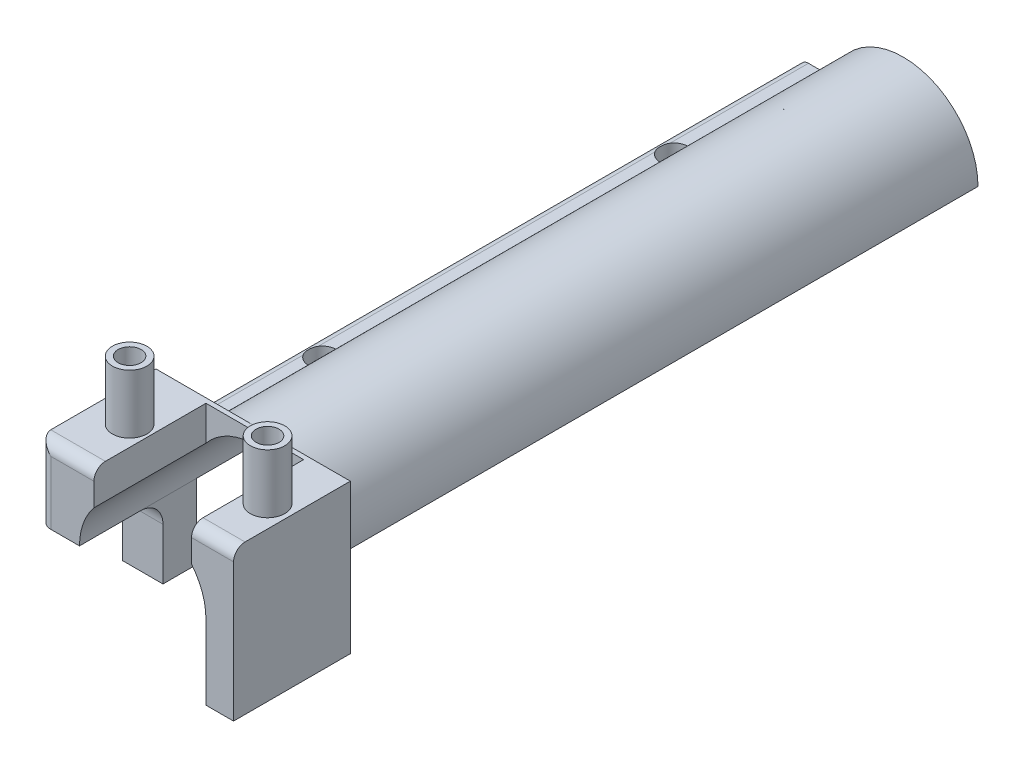
SolidWorks part; units mm, degrees
material "ABS"
ref_plane "X-Y Datum" through (0, 0, 0) normal (0, 0, 1) x (1, 0, 0)
ref_plane "X-Z Datum" through (0, 0, 0) normal (0, 1, 0) x (1, 0, 0)
ref_plane "Y-Z Datum" through (0, 0, 0) normal (1, 0, 0) x (0, 0, -1)
sketch "Sketch1" plane through (0, 0, 0) normal (0, 0, 1) x (1, 0, 0)
  line L0 (-13, 0) -> (-18, 0)
  line L1 (-18, 0) -> (-18, -13)
  line L2 (-18, -13) -> (0, -13)
  line L3 (-13, 0) -> (13, 0)
  line L4 (0, 13) -> (-18, 13)
  line L5 (-18, 13) -> (-18, 0)
  line L6 (-18, 3.81) -> (-12.4292, 3.81)
  circle A0 centre (0, 0) radius 13
  circle A1 centre (0, 0) radius 11
  dimension "D3" = 2
  dimension "D2" = 22
  dimension "D1" = 5
  dimension "D4" = 3.81
extrude "Boss-Extrude1" add sketch "Sketch1" along normal blind 112 contours A1 L3 A0 | A0 L6 L5 L0 region at (-12.569, 1.8832, 0) region at (-15.4029, 1.9398, 0)
sketch "Sketch5" plane through (0, 3.81, 0) normal (0, 1, 0) x (1, 0, 0)
  point P0 (-14.5, -86.6)
  point P1 (-14.5, -25.4)
hole_wizard "M4 Clearance Hole2" positions "Sketch5" profile "Sketch6" hole size "M4" standard "ANSI Metric" end condition through all
sketch "Sketch6" plane through (-14.5, 3.81, 86.6) normal (1, 0, 0) x (0, 0, 1)
  line L0 (0, 0) -> (0, 3.81)
  line L1 (0, 3.81) -> (2.4, 3.81)
  line L2 (2.4, 3.81) -> (2.4, 0)
  line L5 (2.4, 0) -> (0, 0)
  line L11 (0, -6.35) -> (0, 107.95) construction
  dimension "Thru Hole Dia." = 4.8
  dimension "Thru Hole Depth" = 3.81
sketch "Sketch7" plane through (0, 3.81, 0) normal (0, 1, 0) x (1, 0, 0)
  circle A0 centre (-14.5, -25.4) radius 4
  circle A1 centre (-14.5, -86.6) radius 4
  dimension "D1" = 8
extrude "Cut-Extrude1" cut sketch "Sketch7" along normal through all
fillet "Fillet1" radius 1.5 4 edges at (-12.4292, 3.81, 101.0111) (-12.4292, 3.81, 56) (-18, 3.81, 56) (-12.4292, 3.81, 10.9889)
sketch "Sketch10" plane through (0, 0, 112) normal (0, 0, 1) x (1, 0, 0)
  line L0 (-18, 0) -> (-11, 0) construction
  line L1 (-18, 0) -> (-11, 0)
  line L2 (-18, 2.31) -> (-18, 0) construction
  line L3 (11, 0) -> (13, 0) construction
  line L4 (11, 0) -> (13, 0)
  line L5 (-18, 2.31) -> (-18, 0)
  line L6 (-18, 2.31) -> (-18, 13)
  line L7 (-18, 13) -> (15.8008, 13)
  line L8 (15.8008, 13) -> (15.8008, 0)
  line L9 (15.8008, 0) -> (13, 0)
  arc A0 (11, 0) -> (-11, 0) centre (0, 0) ccw construction
  arc A1 (11, 0) -> (-11, 0) centre (0, 0) ccw
  arc A2 (-16.5, 3.81) -> (-18, 2.31) centre (-16.5, 2.31) ccw construction
  arc A3 (-13.4927, 3.81) -> (-12.0969, 4.7607) centre (-13.4927, 5.31) ccw construction
  arc A4 (13, 0) -> (-12.0969, 4.7607) centre (0, 0) ccw construction
  arc A5 (13, 0) -> (-12.0969, 4.7607) centre (0, 0) ccw
  arc A6 (-13.4927, 3.81) -> (-12.0969, 4.7607) centre (-13.4927, 5.31) ccw
  arc A7 (-16.5, 3.81) -> (-18, 2.31) centre (-16.5, 2.31) ccw
  point P13 (0, 13)
  line M2 (-13.4927, 3.81) -> (-16.5, 3.81)
  arc M3 (-16.5, 3.81) -> (-18, 2.31) centre (-16.5, 2.31) ccw
  line M4 (-18, 2.31) -> (-18, 0)
  line M5 (-18, 0) -> (-11, 0)
  arc M6 (-11, 0) -> (11, 0) centre (0, 0) cw
  line M7 (11, 0) -> (13, 0)
  arc M8 (13, 0) -> (-12.0969, 4.7607) centre (0, 0) ccw
  arc M9 (-12.0969, 4.7607) -> (-13.4927, 3.81) centre (-13.4927, 5.31) cw
extrude "Boss-Extrude2" add sketch "Sketch10" along normal blind 20.32 contours L7 M3 M2 M9 M8 | L7 M8 M9 M2 M3 M4 M5 M6 M7 | L8 M8 region at (-17.6638, 1.155, 112) region at (-13.147, 9.1854, 112) region at (12.2525, 8.2946, 112)
sketch "Sketch12" plane through (0, 13, 0) normal (0, 1, 0) x (1, 0, 0)
  circle A0 centre (12, -122.6) radius 2 construction
  circle A1 centre (-12, -122.6) radius 2 construction
  circle A2 centre (12, -122.6) radius 2
  circle A3 centre (-12, -122.6) radius 2
  circle A4 centre (-12, -122.6) radius 3
  circle A5 centre (12, -122.6) radius 3
  dimension "D1" = 6
  dimension "D2" = 6
extrude "Boss-Extrude4" add sketch "Sketch12" along normal blind 10.2375
sketch "Sketch13" plane through (0, 13, 0) normal (0, 1, 0) x (1, 0, 0)
  line L0 (0, -114.6) -> (0, -130.6) construction
  line L2 (-8.4946, -112.821) -> (8.4946, -112.821)
  line L3 (-8.4946, -112.821) -> (-8.4946, -132.379)
  line L4 (-8.4946, -132.379) -> (8.4946, -132.379)
  line L5 (8.4946, -112.821) -> (8.4946, -132.379)
  line L6 (-8.4946, -112.821) -> (8.4946, -132.379) construction
  line L7 (-8.4946, -132.379) -> (8.4946, -112.821) construction
  point P4 (0, -122.6)
  dimension "D1" = 19.558
  dimension "D2" = 16.9892
extrude "Cut-Extrude4" cut sketch "Sketch13" against normal through all contours L5 L2 L3 L4 region at (0, 13, 122.6)
sketch "Sketch14" plane through (0, 0, 0) normal (0, -1, 0) x (1, 0, 0)
  line L0 (11, 132.32) -> (11, 0) construction
  line L1 (15.8008, 132.32) -> (11, 132.32)
  line L2 (15.8008, 132.32) -> (15.8008, 112.0011)
  line L3 (15.8008, 112.0011) -> (11, 112.0011)
  line L4 (11, 132.32) -> (11, 112.0011)
  line L5 (-11, 132.32) -> (-11, 0) construction
  line L6 (-11, 112.0011) -> (-18, 112.0011)
  line L7 (-11, 112.0011) -> (-11, 117.7964)
  line L8 (-11, 117.7964) -> (-18, 117.7964)
  line L9 (-18, 112.0011) -> (-18, 117.7964)
  line L10 (-18, 132.32) -> (-18, 0) construction
extrude "Boss-Extrude5" add sketch "Sketch14" along normal blind 13
fillet "Fillet2" radius 4 1 edges at (-14.5, 0, 117.7964)
fillet "Fillet3" radius 2 3 edges at (12.1477, 13, 132.32) (-18, 6.5, 132.32) (-13.2473, 13, 132.32)
